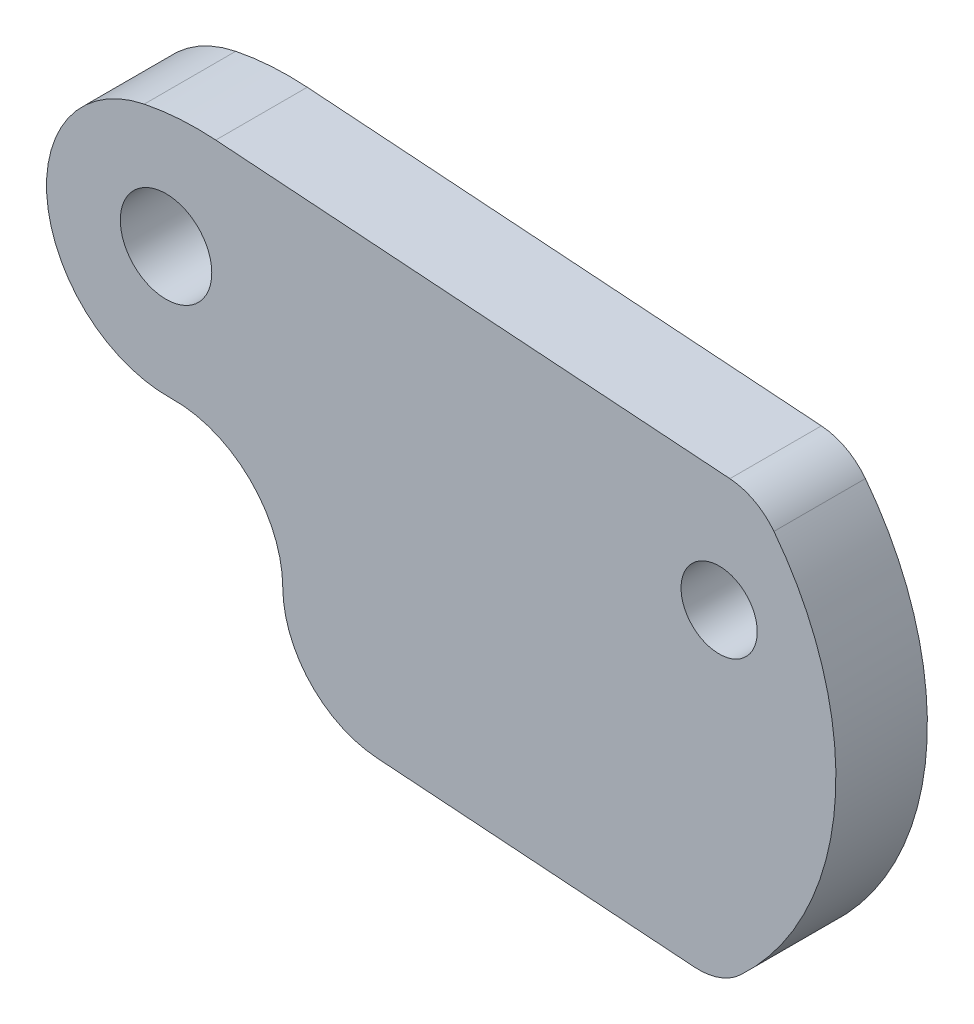
SolidWorks part; units mm, degrees
ref_plane "Plan de face" through (0, 0, 0) normal (0, 0, 1) x (1, 0, 0)
ref_plane "Plan de dessus" through (0, 0, 0) normal (0, 1, 0) x (1, 0, 0)
ref_plane "Plan de droite" through (0, 0, 0) normal (1, 0, 0) x (0, 0, -1)
sketch "Esquisse1" plane through (0, 0, 0) normal (0, 0, 1) x (1, 0, 0)
  line L0 (1174.272, 1712.8262) -> (1173.9944, 1698.3289) construction
  line L1 (1180.8063, 1712.4232) -> (1163.9441, 1713.6097)
  line L2 (1169.2299, 1698.7019) -> (1179.6465, 1697.969)
  circle A0 centre (1162.313, 1709.7715) radius 1.5
  circle A1 centre (1180.4531, 1708.5176) radius 1.25
  arc A2 (1182.2507, 1711.6482) -> (1181.1459, 1698.4967) centre (1174.4951, 1705.6776) cw
  arc A3 (1163.9441, 1713.6097) -> (1161.5984, 1713.4576) centre (1163.3312, 1704.899) ccw
  arc A4 (1161.5984, 1713.4576) -> (1162.4888, 1705.5413) centre (1162.3919, 1709.5386) ccw
  arc A5 (1162.4888, 1705.5413) -> (1166.1419, 1701.996) centre (1162.5753, 1701.9757) cw
  arc A6 (1166.1419, 1701.996) -> (1169.2299, 1698.7019) centre (1169.463, 1702.0148) ccw
  arc A7 (1179.6465, 1697.969) -> (1181.1459, 1698.4967) centre (1179.7869, 1699.964) ccw
  arc A8 (1180.8063, 1712.4232) -> (1182.2507, 1711.6482) centre (1180.6659, 1710.4282) cw
  dimension "D3" = 3
  dimension "D4" = 2.5
  dimension "D5" = 2
  dimension "D1" = 14.5
  dimension "D2" = 14.5
base flange "Tôle de base pliée1" sketch "Esquisse1" thickness 3 reverse thickness direction no parameters "D1"=1.5
sketch "Lignes de pliage1" [suppressed] plane through (0, 0, 0) normal (0, 1, 0) x (1, 0, 0)
sketch "Cube de visualisation1" [suppressed] plane through (0, 0, 0) normal (0, 1, 0) x (1, 0, 0)
sheet metal parameters "Tôlerie1" thickness 3 parameters "D1"=1.5
flat pattern "Etat déplié1" [suppressed]
sketch "Lignes de pliage2" plane through (0, 0, 0) normal (0, 1, 0) x (1, 0, 0)
sketch3d "Cube de visualisation2" [suppressed]
  line L0 (-4.6353, 9.08, 0) -> (21.4308, 7.2459, 0) construction
  line L1 (-5.653, -5.3842, 0) -> (20.413, -7.2183, 0) construction
  line L2 (-4.6353, 9.08, 0) -> (-5.653, -5.3842, 0) construction
  line L3 (21.4308, 7.2459, 0) -> (20.413, -7.2183, 0) construction
